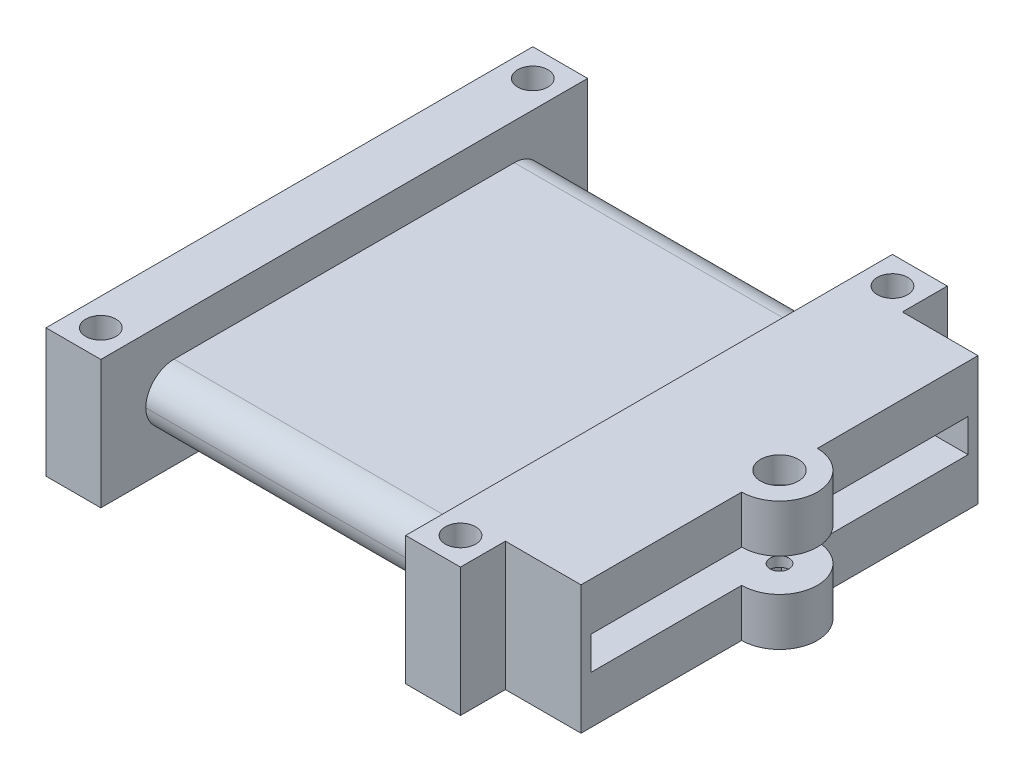
SolidWorks part; units mm, degrees
ref_plane "Front Plane" through (0, 0, 0) normal (0, 0, 1) x (1, 0, 0)
ref_plane "Top Plane" through (0, 0, 0) normal (0, 1, 0) x (1, 0, 0)
ref_plane "Right Plane" through (0, 0, 0) normal (1, 0, 0) x (0, 0, -1)
sketch "Sketch1" plane through (0, 0, 0) normal (1, 0, 0) x (0, 0, -1)
  line L0 (21, 5.9) -> (21, 0) construction
  line L1 (0, 0) -> (42, 0)
  line L2 (0, 0) -> (0, 5.9)
  line L3 (0, 5.9) -> (42, 5.9)
  line L4 (42, 0) -> (42, 5.9)
  line L6 (1.05, 1.2) -> (40.95, 1.2)
  line L7 (1.05, 1.2) -> (1.05, 4.7)
  line L8 (1.05, 4.7) -> (40.95, 4.7)
  line L9 (40.95, 1.2) -> (40.95, 4.7)
  line L10 (1.05, 1.2) -> (40.95, 4.7) construction
  line L11 (1.05, 4.7) -> (40.95, 1.2) construction
  point P7 (21, 2.95)
  dimension "D1" = 42
  dimension "D2" = 5.9
  dimension "D3" = 3.5
  dimension "D4" = 39.9
extrude "Boss-Extrude1" add sketch "Sketch1" along normal blind 32.25
fillet "Fillet2" radius 3 4 edges at (16.125, 0, -42) (16.125, 0, 0) (16.125, 5.9, 0) (16.125, 5.9, -42)
sketch "Sketch2" plane through (32.25, 0, 0) normal (1, 0, 0) x (0, 0, -1)
  line L0 (21, 5.9) -> (21, 0) construction
  line L1 (39, 5.9) -> (3, 5.9) construction
  line L2 (3, 0) -> (39, 0) construction
  line L4 (-4.75, -3.85) -> (46.75, -3.85)
  line L5 (-4.75, -3.85) -> (-4.75, 9.75)
  line L6 (-4.75, 9.75) -> (46.75, 9.75)
  line L7 (46.75, -3.85) -> (46.75, 9.75)
  line L8 (-4.75, -3.85) -> (46.75, 9.75) construction
  line L9 (-4.75, 9.75) -> (46.75, -3.85) construction
  line L14 (40.95, 1.2) -> (1.05, 1.2)
  line L15 (40.95, 1.2) -> (40.95, 4.7)
  line L16 (40.95, 4.7) -> (1.05, 4.7)
  line L17 (1.05, 1.2) -> (1.05, 4.7)
  line L18 (40.95, 1.2) -> (1.05, 4.7) construction
  line L19 (40.95, 4.7) -> (1.05, 1.2) construction
  point P6 (21, 2.95)
  point P11 (21, 2.95)
  point P12 (21, 2.95)
  dimension "D1" = 13.6
  dimension "D2" = 51.5
extrude "Boss-Extrude2" add sketch "Sketch2" along normal blind 5.8
sketch "Sketch3" plane through (0, 0, 0) normal (-1, 0, 0) x (0, 0, 1)
  line L0 (-21, 5.9) -> (-21, 0) construction
  line L1 (-39, 5.9) -> (-3, 5.9) construction
  line L2 (-3, 0) -> (-39, 0) construction
  line L4 (4.75, -3.85) -> (-46.75, -3.85)
  line L5 (4.75, -3.85) -> (4.75, 9.75)
  line L6 (4.75, 9.75) -> (-46.75, 9.75)
  line L7 (-46.75, -3.85) -> (-46.75, 9.75)
  line L8 (4.75, -3.85) -> (-46.75, 9.75) construction
  line L9 (4.75, 9.75) -> (-46.75, -3.85) construction
  line L10 (-1.05, 1.2) -> (-40.95, 1.2)
  line L11 (-1.05, 1.2) -> (-1.05, 4.7)
  line L12 (-1.05, 4.7) -> (-40.95, 4.7)
  line L13 (-40.95, 1.2) -> (-40.95, 4.7)
  line L14 (-1.05, 1.2) -> (-40.95, 4.7) construction
  line L15 (-1.05, 4.7) -> (-40.95, 1.2) construction
  point P6 (-21, 2.95)
  point P12 (-21, 2.95)
extrude "Boss-Extrude3" add sketch "Sketch3" along normal blind 5.8
sketch "Sketch4" plane through (0, 9.75, 0) normal (0, 1, 0) x (1, 0, 0)
  line L0 (-2.9, 46.75) -> (-2.9, 43.85) construction
  line L1 (-5.8, 46.75) -> (0, 46.75) construction
  line L2 (35.15, 46.75) -> (35.15, 43.85) construction
  line L3 (38.05, 46.75) -> (32.25, 46.75) construction
  line L4 (-2.9, -4.75) -> (-2.9, -1.85) construction
  line L5 (-5.8, -4.75) -> (0, -4.75) construction
  line L6 (35.15, -4.75) -> (35.15, -1.85) construction
  line L7 (38.05, -4.75) -> (32.25, -4.75) construction
  circle A0 centre (-2.9, 43.85) radius 1.6
  circle A1 centre (35.15, 43.85) radius 1.6
  circle A2 centre (-2.9, -1.85) radius 1.6
  circle A3 centre (35.15, -1.85) radius 1.6
  dimension "D2" = 3.2
  dimension "D4" = 3.2
  dimension "D6" = 3.2
  dimension "D8" = 3.2
  dimension "D1" = 2.9
  dimension "D3" = 2.9
  dimension "D5" = 2.9
  dimension "D7" = 2.9
extrude "Cut-Extrude1" cut sketch "Sketch4" against normal through all
sketch "Sketch6" plane through (38.05, 0, 0) normal (1, 0, 0) x (0, 0, -1)
  line L0 (46.75, -3.85) -> (46.75, 9.75) construction
  line L1 (-4.75, -3.85) -> (46.75, -3.85)
  line L2 (-4.75, -3.85) -> (-4.75, 3.35)
  line L3 (-4.75, 3.35) -> (46.75, 3.35)
  line L4 (46.75, -3.85) -> (46.75, 3.35)
  dimension "D1" = 7.2
extrude "Cut-Extrude2" [suppressed] cut sketch "Sketch6" against normal blind 5.8
sketch "Sketch7" plane through (-5.8, 0, 0) normal (-1, 0, 0) x (0, 0, 1)
  line L0 (4.75, -3.85) -> (4.75, 9.75) construction
  line L1 (-46.75, -3.85) -> (4.75, -3.85)
  line L2 (-46.75, -3.85) -> (-46.75, 3.35)
  line L3 (-46.75, 3.35) -> (4.75, 3.35)
  line L4 (4.75, -3.85) -> (4.75, 3.35)
  dimension "D1" = 7.2
extrude "Cut-Extrude3" [suppressed] cut sketch "Sketch7" against normal blind 5.8
sketch "Sketch8" plane through (0, 9.75, 0) normal (0, 1, 0) x (1, 0, 0)
  line L1 (0, 41.9996) -> (32.25, 41.9996) construction
  line L2 (38.05, 46.75) -> (38.05, -4.75) construction
  line L3 (46.05, 25) -> (46.05, 41.9996)
  line L4 (46.05, 41.9996) -> (38.05, 41.9996)
  line L5 (46.05, 17) -> (46.05, 0.0004)
  line L6 (46.05, 0.0004) -> (38.05, 0.0004)
  line L12 (-42.1211, 21) -> (79.5205, 21) construction
  line L13 (-5.8, -4.75) -> (-5.8, 46.75) construction
  circle A0 centre (46.05, 21) radius 4
  point P17 (-5.8, 21)
  line M5 (38.05, -4.75) -> (38.05, 46.75)
  dimension "D1" = 8
  dimension "D2" = 8
extrude "Boss-Extrude4" add sketch "Sketch8" against normal blind 13.6 contours A0 L3 L4 M5 | A0 L6 L5 M5 | A0 | A0 L12 region at (41.8639, 9.75, -32.2114) region at (46.05, 9.75, -22.6977) region at (46.05, 9.75, -19.3023) region at (41.8639, 9.75, -9.7886)
hole_wizard "CSK for M2 Flat Head Machine Screw1" positions "Sketch12" profile "Sketch13" countersink size "M2" standard "ANSI Metric" end condition through all
sketch "Sketch12" plane through (0, 9.75, 0) normal (0, 1, 0) x (1, 0, 0)
  point P0 (46.05, 21)
sketch "Sketch13" plane through (46.05, 9.75, -21) normal (1, 0, 0) x (0, 0, 1)
  line L0 (0, 0) -> (0, 13.6)
  line L1 (0, 13.6) -> (1, 13.6)
  line L2 (1, 13.6) -> (1, 3.75)
  line L3 (1, 3.75) -> (2, 2.75)
  line L4 (2, 2.75) -> (2, 0)
  line L6 (2, 0) -> (0, 0)
  line L7 (-1, 3.75) -> (-2, 2.75) construction
  line L11 (0, -6.35) -> (0, 107.95) construction
  dimension "Thru Hole Dia." = 2
  dimension "Thru Hole Depth" = 13.6
  dimension "C'Sink Dia." = 4
  dimension "C'Sink Angle" = 90
  dimension "Head Clearance" = 2.75
sketch "Sketch14" plane through (0, -3.85, 0) normal (0, -1, 0) x (1, 0, 0)
  line L1 (43.6716, -20.5274) -> (44.4516, -22.8234)
  line L2 (44.4516, -22.8234) -> (46.8299, -23.296)
  line L3 (46.8299, -23.296) -> (48.4284, -21.4726)
  line L4 (48.4284, -21.4726) -> (47.6484, -19.1766)
  line L5 (47.6484, -19.1766) -> (45.2701, -18.704)
  line L6 (45.2701, -18.704) -> (43.6716, -20.5274)
  circle A0 centre (46.05, -21) radius 2.1 construction
  dimension "D1" = 4.2
extrude "Cut-Extrude4" cut sketch "Sketch14" against normal blind 4
sketch "Sketch15" plane through (-5.8, 0, 0) normal (-1, 0, 0) x (0, 0, 1)
  line L1 (-40.95, 1.2) -> (-1.05, 1.2)
  line L2 (-40.95, 1.2) -> (-40.95, 4.7)
  line L3 (-40.95, 4.7) -> (-1.05, 4.7)
  line L4 (-1.05, 1.2) -> (-1.05, 4.7)
  line L5 (-46.75, -3.85) -> (-40.95, -3.85)
  line L6 (-46.75, -3.85) -> (-46.75, -1.85)
  line L7 (-46.75, -1.85) -> (-40.95, -1.85)
  line L8 (-40.95, -3.85) -> (-40.95, -1.85)
  line L9 (4.75, -3.85) -> (-1.05, -3.85)
  line L10 (4.75, -3.85) -> (4.75, -1.85)
  line L11 (4.75, -1.85) -> (-1.05, -1.85)
  line L12 (-1.05, -3.85) -> (-1.05, -1.85)
  dimension "D1" = 5.8
  dimension "D2" = 2
  dimension "D3" = 5.8
  dimension "D4" = 2
extrude "Cut-Extrude5" cut sketch "Sketch15" against normal through all contours L2 L1 L4 L3
